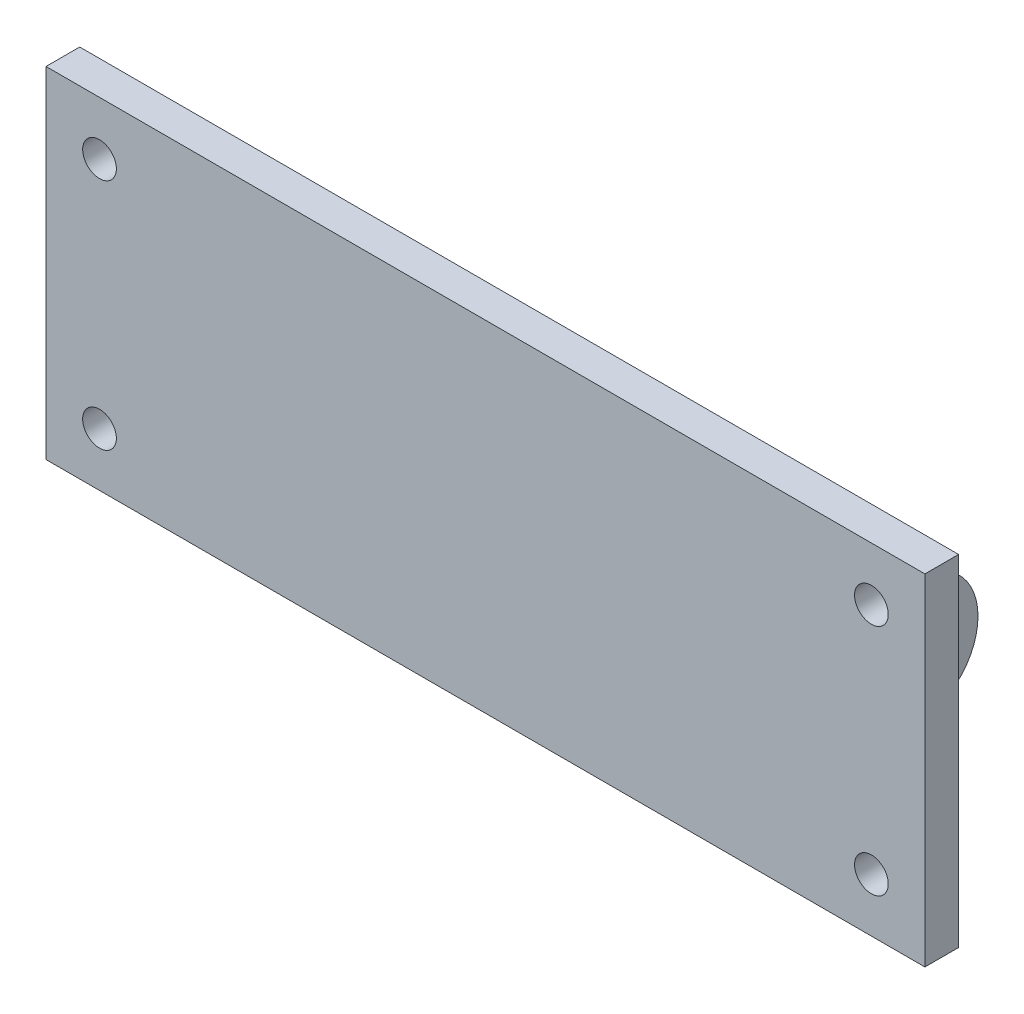
SolidWorks part; units mm, degrees
ref_plane "Front Plane" through (0, 0, 0) normal (0, 0, 1) x (1, 0, 0)
ref_plane "Top Plane" through (0, 0, 0) normal (0, 1, 0) x (1, 0, 0)
ref_plane "Right Plane" through (0, 0, 0) normal (1, 0, 0) x (0, 0, -1)
sketch "Sketch1" plane through (0, 0, 0) normal (0, 0, 1) x (1, 0, 0)
  line L0 (-57.0556, -366.875) -> (-37.0556, -366.875)
  line L5 (-57.0556, -366.875) -> (-57.0556, -396.875)
  line L6 (-57.0556, -396.875) -> (-37.0556, -396.875)
  line L11 (-37.0556, -366.875) -> (-37.0556, -396.875)
  line L12 (-57.0556, -366.875) -> (-37.0556, -396.875) construction
  line L13 (-57.0556, -396.875) -> (-37.0556, -366.875) construction
  line L14 (80.7444, -366.875) -> (100.7444, -366.875)
  line L15 (80.7444, -366.875) -> (80.7444, -396.875)
  line L16 (80.7444, -396.875) -> (100.7444, -396.875)
  line L17 (100.7444, -366.875) -> (100.7444, -396.875)
  line L18 (80.7444, -366.875) -> (100.7444, -396.875) construction
  line L19 (80.7444, -396.875) -> (100.7444, -366.875) construction
  line L21 (126.1444, -341.475) -> (-82.4556, -341.475)
  line L22 (126.1444, -341.475) -> (126.1444, -422.275)
  line L23 (126.1444, -422.275) -> (-82.4556, -422.275)
  line L24 (-82.4556, -341.475) -> (-82.4556, -422.275)
  line L25 (126.1444, -341.475) -> (-82.4556, -422.275) construction
  line L26 (126.1444, -422.275) -> (-82.4556, -341.475) construction
  circle A0 centre (113.4444, -354.175) radius 4
  circle A1 centre (-69.7556, -409.575) radius 4
  circle A3 centre (113.4444, -409.575) radius 4
  circle A4 centre (-69.7556, -354.175) radius 4
  point P0 (-47.0556, -381.875)
  point P5 (90.7444, -381.875)
  point P10 (21.8444, -381.875)
  dimension "D7" = 8
  dimension "D8" = 12.7
  dimension "D10" = 12.7
  dimension "D11" = 25.4
  dimension "D14" = 8
  dimension "D15" = 12.7
  dimension "D17" = 8
  dimension "D18" = 8
  dimension "D19" = 12.7
  dimension "D20" = 12.7
  dimension "D21" = 12.7
  dimension "D22" = 12.7
  dimension "D1" = 20
  dimension "D2" = 30
  dimension "D3" = 20
  dimension "D4" = 30
  dimension "D5" = 117.8
  dimension "D6" = 0
  dimension "D9" = 25.4
  dimension "D12" = 25.4
  dimension "D13" = 25.4
  dimension "D16" = 12.7
extrude "Boss-Extrude1" add sketch "Sketch1" along normal blind 8 contours L17 L14 L15 L16 | L11 L0 L5 L6 | L21 L24 L23 L22 A3 A4 A1 A0 L14 L17 L16 L15 L0 L11 L6 L5 region at (-47.0556, -381.875, 0) region at (90.7444, -381.875, 0) region at (21.8444, -381.875, 0)
extrude "Boss-Extrude2" add sketch "Sketch1<3>" against normal blind 30 contours L17 L14 L15 L16 | L11 L0 L5 L6 region at (-47.0556, -381.875, 0) region at (90.7444, -381.875, 0)
sketch "Sketch1<3>" plane through (0, 0, 0) normal (0, 0, 1) x (1, 0, 0) same geometry as "Sketch1"
fillet "Fillet1" radius 5 4 edges at (-47.0556, -366.875, 0) (-47.0556, -396.875, 0) (90.7444, -396.875, 0) (90.7444, -366.875, 0)
fillet "Fillet2" radius 15 4 edges at (90.7444, -366.875, -30) (90.7444, -396.875, -30) (-47.0556, -396.875, -30) (-47.0556, -366.875, -30)
sketch "Sketch2" plane through (100.7444, 0, 0) normal (1, 0, 0) x (0, 0, -1)
  line L0 (0, -341.475) -> (0, -422.275) construction
  line L1 (15, -366.875) -> (5, -366.875) construction
  circle A0 centre (15, -381.875) radius 5
  dimension "D1" = 10
  dimension "D2" = 15
  dimension "D3" = 15
extrude "Cut-Extrude1" cut sketch "Sketch2" against normal through all
